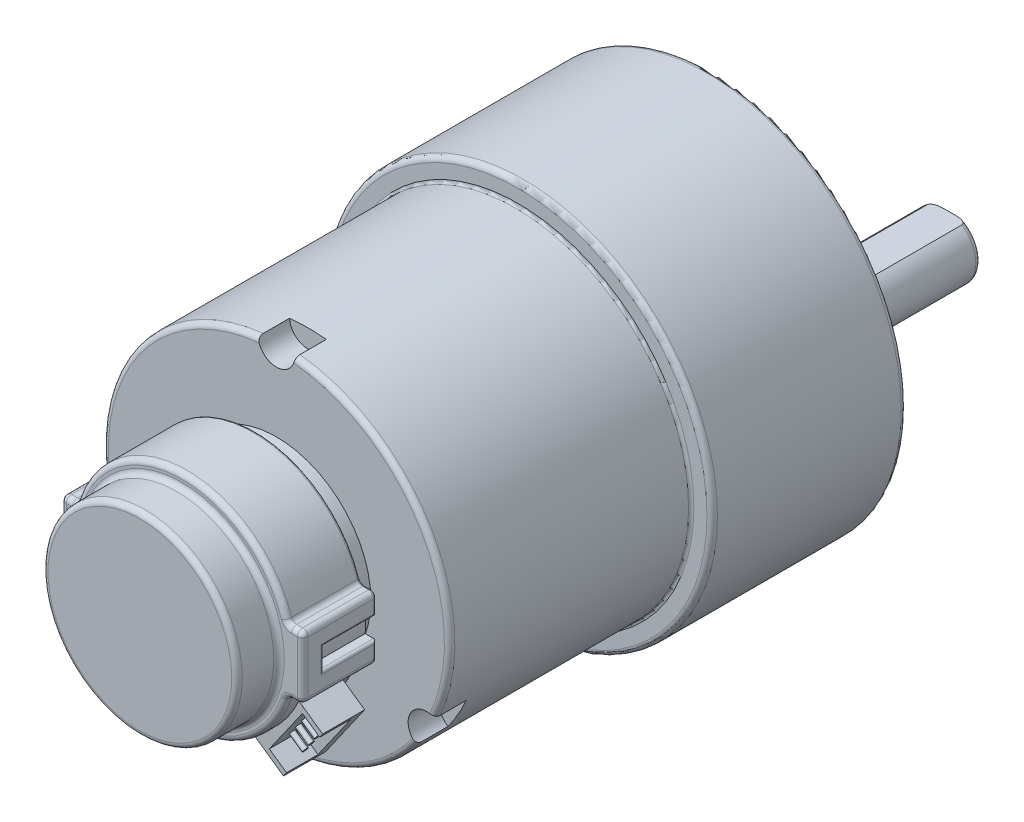
SolidWorks part; units mm, degrees
ref_plane "Front Plane" through (0, 0, 0) normal (0, 0, 1) x (1, 0, 0)
ref_plane "Top Plane" through (0, 0, 0) normal (0, 1, 0) x (1, 0, 0)
ref_plane "Right Plane" through (0, 0, 0) normal (1, 0, 0) x (0, 0, -1)
sketch "Sketch2" plane through (0, 0, 0) normal (0, 0, 1) x (1, 0, 0)
  circle A0 centre (0, 0) radius 18.5
  dimension "D1" = 37
extrude "Boss-Extrude1" add sketch "Sketch2" along normal blind 18.5
sketch "Sketch3" plane through (0, 0, 0) normal (0, 0, -1) x (-1, 0, 0)
  line L0 (15.5, 0) -> (-15.5, 0) construction
  line L1 (-13.8293, -7) -> (0, -7) construction
  line L2 (0, -24.9481) -> (0, 22.7839) construction
  line L3 (0, -7) -> (13.8293, -7) construction
  line L4 (0, 0) -> (-7.75, 13.4234) construction
  line L5 (0, 0) -> (-7.75, -13.4234) construction
  circle A0 centre (0, 0) radius 15.5 construction
  arc A1 (8.3432, -8.625) -> (-8.3432, -8.625) centre (0, -7) ccw
  circle A2 centre (-13.8293, -7) radius 2
  circle A3 centre (13.8293, -7) radius 2
  circle A4 centre (0, 15.5) radius 2
  circle A5 centre (-7.75, -13.4234) radius 1.5
  circle A6 centre (-15.5, 0) radius 1.5
  circle A7 centre (-7.75, 13.4234) radius 1.5
  circle A8 centre (15.5, 0) radius 1.5
  arc A9 (8.3432, -8.625) -> (-8.3432, -8.625) centre (0, 0) ccw
  dimension "D1" = 31
  dimension "D3" = 17
  dimension "D4" = 4
  dimension "D7" = 3
  dimension "D8" = 24
  dimension "D2" = 7
  dimension "D5" = 120
  dimension "D6" = 120
extrude "Cut-Extrude1" cut sketch "Sketch3" against normal blind 0.5
sketch "Sketch4" plane through (0, 0, 0) normal (0, 0, -1) x (-1, 0, 0)
  arc A0 (8.3432, -8.625) -> (-8.3432, -8.625) centre (0, -7) ccw construction
  arc A1 (8.3432, -8.625) -> (-8.3432, -8.625) centre (0, -7) ccw construction
  circle A2 centre (0, -7) radius 6
  dimension "D1" = 12
extrude "Boss-Extrude2" add sketch "Sketch4" along normal blind 4.6
sketch "Sketch5" plane through (0, 0, -4.6) normal (0, 0, -1) x (-1, 0, 0)
  circle A0 centre (0, -7) radius 6 construction
  circle A1 centre (0, -7) radius 6 construction
  circle A2 centre (0, -7) radius 3
  dimension "D1" = 6
extrude "Boss-Extrude3" add sketch "Sketch5" along normal blind 18
sketch "Sketch6" plane through (0, 0, -22.6) normal (0, 0, -1) x (-1, 0, 0)
  line L0 (1.6583, -4.5) -> (-1.6583, -4.5)
  line L1 (0, -10) -> (-6.6128, -10) construction
  circle A0 centre (0, -7) radius 3 construction
  arc A1 (1.6583, -4.5) -> (-1.6583, -4.5) centre (0, -7) ccw
  dimension "D1" = 5.5
extrude "Cut-Extrude2" cut sketch "Sketch6" against normal blind 12
sketch "Sketch7" plane through (0, 0, 18.5) normal (0, 0, 1) x (1, 0, 0)
  circle A0 centre (0, 0) radius 16.5
  dimension "D1" = 33
extrude "Boss-Extrude4" add sketch "Sketch7" along normal blind 23
sketch "Sketch8" plane through (0, 0, 41.5) normal (0, 0, 1) x (1, 0, 0)
  line L0 (0, 0) -> (14.2894, -8.25) construction
  line L1 (0, 0) -> (-14.2894, -8.25) construction
  line L2 (0, 0) -> (0, 16.5) construction
  circle A0 centre (0, 0) radius 16.5 construction
  circle A1 centre (0, 0) radius 16.5 construction
  circle A2 centre (0, 16.5) radius 1.75
  circle A3 centre (14.2894, -8.25) radius 1.75
  circle A4 centre (-14.2894, -8.25) radius 1.75
  dimension "D3" = 3.5
  dimension "D1" = 120
  dimension "D2" = 120
extrude "Cut-Extrude3" cut sketch "Sketch8" against normal blind 3
sketch "Sketch9" plane through (0, 0, 41.5) normal (0, 0, 1) x (1, 0, 0)
  circle A0 centre (0, 0) radius 9
  dimension "D1" = 18
extrude "Boss-Extrude5" add sketch "Sketch9" along normal blind 2
sketch "Sketch10" plane through (0, 0, 43.5) normal (0, 0, 1) x (1, 0, 0)
  line L1 (-11.5, -3) -> (-10.0623, -3)
  line L2 (-11.5, -3) -> (-11.5, -1)
  line L3 (-11.5, 3) -> (-10.0623, 3)
  line L5 (-11.5, -3) -> (-9.5, 3) construction
  line L6 (-11.5, 3) -> (-9.5, -3) construction
  line L7 (10.0623, -3) -> (11.5, -3)
  line L9 (10.0623, 3) -> (11.5, 3)
  line L10 (11.5, -3) -> (11.5, -1)
  line L11 (9.5, -3) -> (11.5, 3) construction
  line L12 (9.5, 3) -> (11.5, -3) construction
  line L13 (10.4523, -1) -> (11.5, -1)
  line L14 (11.5, 1) -> (11.5, 3)
  line L15 (10.4523, 1) -> (11.5, 1)
  line L17 (9.5, -1) -> (11.5, 1) construction
  line L18 (9.5, 1) -> (11.5, -1) construction
  line L19 (-11.5, -1) -> (-10.4523, -1)
  line L21 (-11.5, 1) -> (-10.4523, 1)
  line L22 (-11.5, 1) -> (-11.5, 3)
  line L23 (-11.5, -1) -> (-9.5, 1) construction
  line L24 (-11.5, 1) -> (-9.5, -1) construction
  line L25 (9.5, -1) -> (9.4675, -0.9837)
  arc A0 (-10.0623, -3) -> (10.0623, -3) centre (0, 0) ccw
  arc A1 (-10.4523, 1) -> (-10.4523, -1) centre (0, 0) ccw
  arc A2 (10.0623, 3) -> (-10.0623, 3) centre (0, 0) ccw
  arc A3 (10.4523, -1) -> (10.4523, 1) centre (0, 0) ccw
  point P3 (-10.5, 0)
  point P8 (10.5, 0)
  point P13 (10.5, 0)
  point P18 (-10.5, 0)
  circle M1 centre (0, 0) radius 9
  dimension "D1" = 21
  dimension "D2" = 6
  dimension "D3" = 2
  dimension "D4" = 6
  dimension "D5" = 2
  dimension "D6" = 1
  dimension "D7" = 1
  dimension "D8" = 2
  dimension "D9" = 1.4377
  dimension "D10" = 1.4377
  dimension "D11" = 2
extrude "Boss-Extrude6" add sketch "Sketch10" along normal blind 7 contours L13 A3 L15 L14 L9 A2 L3 L22 L21 A1 L19 L2 L1 A0 L7 L10 | M1 region at (-11.1886, -2, 43.5) region at (0, 0, 43.5)
sketch "Sketch11" plane through (0, 0, 50.5) normal (0, 0, 1) x (1, 0, 0)
  line L1 (-11.5, 1) -> (-10.4523, 1)
  line L2 (-11.5, 1) -> (-11.5, -1)
  line L3 (-11.5, -1) -> (-10.4523, -1)
  line L4 (-10.4523, 1) -> (-10.4523, -1)
  line L5 (10.4523, 1) -> (11.5, 1)
  line L6 (10.4523, 1) -> (10.4523, -1)
  line L7 (10.4523, -1) -> (11.5, -1)
  line L8 (11.5, 1) -> (11.5, -1)
  arc A0 (10.4523, -1) -> (10.4523, 1) centre (0, 0) ccw construction
extrude "Boss-Extrude7" add sketch "Sketch11" against normal blind 2
sketch "Sketch12" plane through (0, 0, 50.5) normal (0, 0, 1) x (1, 0, 0)
  circle A0 centre (0, 0) radius 9.25
  dimension "D1" = 18.5
extrude "Boss-Extrude8" add sketch "Sketch12" along normal blind 4
fillet "Fillet1" radius 0.5 18 edges at (-10.7812, -3, 50.5) (-10.7812, 3, 50.5) (10.7812, 3, 50.5) (10.7812, -3, 50.5) (-10.0623, -3, 47) (-11.5, -3, 47) (-11.5, 0, 50.5) (-11.5, 3, 47) (-10.0623, 3, 47) (11.5, 3, 47) (10.0623, 3, 47) (10.0623, -3, 47) (11.5, -3, 47) (11.5, 0, 50.5) (0, -10.5, 50.5) (0, 10.5, 50.5) (9.25, 0, 50.5) (9.25, 0, 54.5)
fillet "Fillet2" radius 0.5 8 edges at (0, -10, -22.6) (-6, -7, -4.6) (6, -7, 0) (18.5, 0, 0) (18.5, 0, 18.5) (-14.2894, 8.25, 41.5) (0, -16.5, 41.5) (14.2894, 8.25, 41.5)
fillet "Fillet3" radius 0.25 35 edges at (-11.5, 1.75, 43.5) (-11.3536, 2.8536, 43.5) (-10.7142, 3, 43.5) (-10.1364, 3.0941, 43.5) (0, 10.5, 43.5) (10.1364, 3.0941, 43.5) (10.7142, 3, 43.5) (11.3536, 2.8536, 43.5) (-11.5, -1.75, 43.5) (-11.3536, -2.8536, 43.5) (-10.7142, -3, 43.5) (-10.1364, -3.0941, 43.5) (11.5, -1.75, 43.5) (11.3536, -2.8536, 43.5) (10.7142, -3, 43.5) (10.1364, -3.0941, 43.5) (-11.5, -1, 46) (-11.5, 0, 48.5) (-11.5, 1, 46) (11.5, 1.75, 43.5) (0, -10.5, 43.5) (11.5, -1, 46) (11.5, 0, 48.5) (11.5, 1, 46) (16.5, 0, 18.5) (11.8293, -7, 0.5) (-2, 15.5, 0.5) (-15.8293, -7, 0.5) (-15.8293, -7, 0) (-2, 15.5, 0) (11.8293, -7, 0) (0, 12, 0) (0, 12, 0.5) (0, 1.5, 0) (0, 1.5, 0.5)
ref_plane "Plane1" through (8.2492, -5.7761, 0) normal (0.8192, -0.5736, 0) x (0, 0, -1)
sketch "Sketch13" plane through (8.2492, -5.7761, 0) normal (0.8192, -0.5736, 0) x (0, 0, -1)
  line L1 (-44.9519, 2.0048) -> (-48.9519, 2.0048)
  line L2 (-44.9519, 2.0048) -> (-44.9519, -4.4952)
  line L3 (-44.9519, -4.4952) -> (-48.9519, -4.4952)
  line L4 (-48.9519, 2.0048) -> (-48.9519, -4.4952)
  dimension "D1" = 4
  dimension "D2" = 6.5
extrude "Boss-Extrude9" add sketch "Sketch13" along normal blind 3 and the other way blind 1
sketch "Sketch14" plane through (10.7066, -7.4969, 0) normal (0.8192, -0.5736, 0) x (0, 0, -1)
  line L0 (-48.9519, 2.0048) -> (-48.9519, -4.4952) construction
  line L1 (-48.9519, 1.5048) -> (-45.9519, 1.5048)
  line L2 (-48.9519, 1.5048) -> (-48.9519, -3.9952)
  line L3 (-48.9519, -3.9952) -> (-45.9519, -3.9952)
  line L4 (-45.9519, 1.5048) -> (-45.9519, -3.9952)
  line L5 (-48.9519, 2.0048) -> (-44.9519, 2.0048) construction
  line L6 (-48.9519, -4.4952) -> (-44.9519, -4.4952) construction
  line L7 (-44.9519, -4.4952) -> (-44.9519, 2.0048) construction
  point P8 (-46.9519, -4.4952)
  dimension "D1" = 0.5
  dimension "D2" = 0.5
  dimension "D3" = 1
extrude "Cut-Extrude4" cut sketch "Sketch14" against normal blind 2
sketch "Sketch15" plane through (9.0683, -6.3497, 0) normal (0.8192, -0.5736, 0) x (0, 0, -1)
  line L0 (-47.4519, 1.5048) -> (-47.4519, -3.9952) construction
  line L1 (-45.9519, 1.5048) -> (-48.9519, 1.5048) construction
  line L2 (-48.9519, -3.9952) -> (-45.9519, -3.9952) construction
  circle A0 centre (-47.4519, 0.2158) radius 0.25
  circle A1 centre (-47.4519, -0.7842) radius 0.25
  circle A2 centre (-47.4519, -1.7842) radius 0.25
  circle A3 centre (-47.4519, -2.7842) radius 0.25
  dimension "D1" = 0.5
  dimension "D2" = 1
  dimension "D3" = 1
  dimension "D4" = 1
extrude "Boss-Extrude10" add sketch "Sketch15" along normal blind 1.5
sketch "Sketch16" plane through (0, 0, 0.5) normal (0, 0, -1) x (-1, 0, 0)
  line L0 (-1.7, 10) -> (-1.7, 7.3)
  line L1 (-2.5, 7) -> (1, 7)
  line L2 (-2.5, 7) -> (-2.5, 10)
  line L3 (-2.5, 10) -> (-1.7, 10)
  line L4 (2.5, 7) -> (2.5, 10)
  line L5 (0, 8.5) -> (2.5, 8.5) construction
  line L6 (0, 8.5) -> (-2.5, 8.5) construction
  line L7 (-1.7, 7.3) -> (1, 7.3)
  line L8 (1, 7.3) -> (1, 7)
  line L9 (1.7, 7) -> (1.7, 9.7)
  line L10 (1.7, 9.7) -> (-1, 9.7)
  line L11 (-1, 9.7) -> (-1, 10)
  line L12 (-1, 10) -> (2.5, 10)
  line L13 (1.7, 7) -> (2.5, 7)
  circle A0 centre (0, 8.5) radius 0.75
  point P0 (0, 8.5)
  dimension "D8" = 1.5
  dimension "D1" = 3
  dimension "D2" = 0.8
  dimension "D3" = 3.5
  dimension "D4" = 0.3
  dimension "D5" = 2.5
  dimension "D6" = 2.5
  dimension "D7" = 8.5
extrude "Boss-Extrude11" add sketch "Sketch16" along normal blind 0.5
sketch "Sketch17" plane through (0, 0, 0.5) normal (0, 0, -1) x (-1, 0, 0)
  line L0 (-8.4137, 3.3841) -> (7.3149, 3.3841) construction
  text T0 "PAT.90153" font "Century Gothic" height 2.5
extrude "Boss-Extrude12" add sketch "Sketch17" along normal blind 0.5
